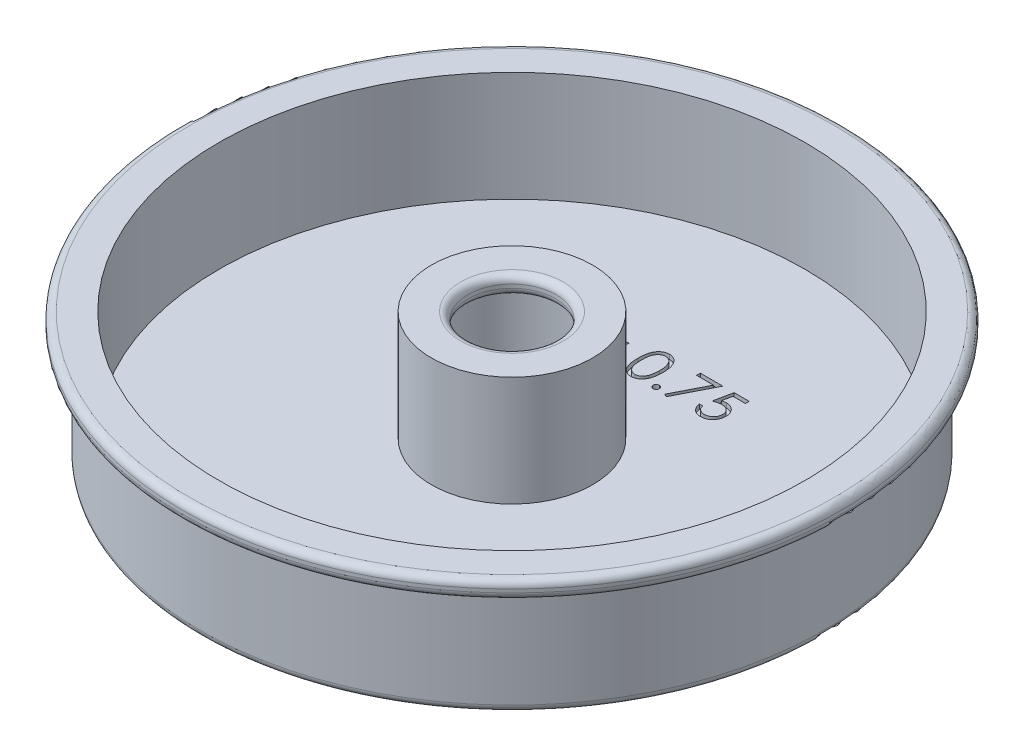
SolidWorks part; units mm, degrees
ref_plane "Front Plane" through (0, 0, 0) normal (0, 0, 1) x (1, 0, 0)
ref_plane "Top Plane" through (0, 0, 0) normal (0, 1, 0) x (1, 0, 0)
ref_plane "Right Plane" through (0, 0, 0) normal (1, 0, 0) x (0, 0, -1)
sketch "Sketch1" plane through (0, 0, 0) normal (0, 0, 1) x (1, 0, 0)
  line L0 (0, 0) -> (0, 11.1543)
  line L3 (13.97, 15.9118) -> (13.97, -3.1382)
  line L4 (13.97, -3.1382) -> (50.8, -3.1382)
  line L5 (50.8, -3.1382) -> (50.8, 15.9118)
  line L8 (52.705, -6.3132) -> (12.065, -6.3132)
  line L9 (53.975, -5.0432) -> (53.975, 11.5037)
  line L10 (55.245, 12.7737) -> (55.88, 12.7737)
  line L11 (57.15, 14.0437) -> (57.15, 14.6418)
  line L12 (50.8, 15.9118) -> (55.88, 15.9118)
  line L13 (13.97, 15.9118) -> (8.89, 15.9118)
  line L14 (7.62, 14.6418) -> (7.62, 14.0068)
  line L15 (10.795, -5.0432) -> (10.795, 11.4668)
  line L16 (9.525, 12.7368) -> (8.89, 12.7368)
  arc A0 (55.88, 15.9118) -> (57.15, 14.6418) centre (55.88, 14.6418) cw
  arc A1 (57.15, 14.0437) -> (55.88, 12.7737) centre (55.88, 14.0437) cw
  arc A2 (55.245, 12.7737) -> (53.975, 11.5037) centre (55.245, 11.5037) ccw
  arc A3 (53.975, -5.0432) -> (52.705, -6.3132) centre (52.705, -5.0432) cw
  arc A4 (12.065, -6.3132) -> (10.795, -5.0432) centre (12.065, -5.0432) cw
  arc A5 (10.795, 11.4668) -> (9.525, 12.7368) centre (9.525, 11.4668) ccw
  arc A6 (8.89, 12.7368) -> (7.62, 14.0068) centre (8.89, 14.0068) cw
  arc A7 (7.62, 14.6418) -> (8.89, 15.9118) centre (8.89, 14.6418) cw
  dimension "D10" = 1.27
  dimension "D1" = 3.175
  dimension "D2" = 6.35
  dimension "D3" = 3.175
  dimension "D4" = 6.35
  dimension "D5" = 3.175
  dimension "D6" = 13.97
  dimension "D7" = 50.8
  dimension "D8" = 3.1382
  dimension "D9" = 3.175
  dimension "D11" = 19.05
  dimension "D12" = 19.05
revolve "Revolve2" add sketch "Sketch1" angle 360 about L0 region at (13.4271, 6.3868, 0)
sketch "Sketch2" plane through (0, -3.1382, 0) normal (0, 1, 0) x (1, 0, 0)
  text T0 "4 x 0.75" font "Century Gothic" height in points 24
  point P1 (0, 0)
  point P2 (-14.3475, 17.4952)
  point P3 (-15.6183, 17.3364)
  point P4 (-15.36, 19.7719)
extrude "Cut-Extrude1" cut sketch "Sketch2" against normal blind 0.7937
